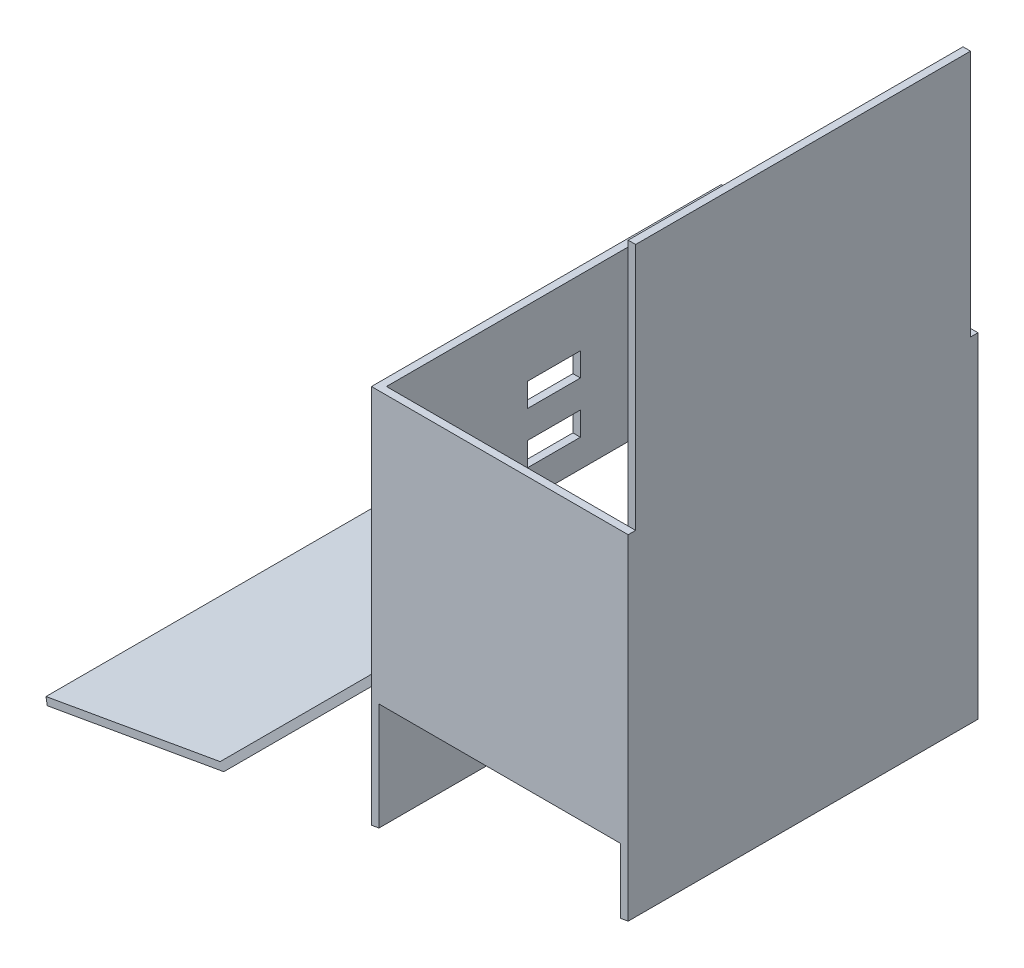
SolidWorks part; units mm, degrees
ref_plane "Front Plane" through (0, 0, 0) normal (0, 0, 1) x (1, 0, 0)
ref_plane "Top Plane" through (0, 0, 0) normal (0, 1, 0) x (1, 0, 0)
ref_plane "Right Plane" through (0, 0, 0) normal (1, 0, 0) x (0, 0, -1)
sketch "Sketch1" plane through (0, 0, 0) normal (0, 1, 0) x (1, 0, 0)
  line L1 (-102.5, 142) -> (102.5, 142)
  line L2 (-102.5, 142) -> (-102.5, -142)
  line L3 (-102.5, -142) -> (102.5, -142)
  line L4 (102.5, 142) -> (102.5, -142)
  line L5 (-102.5, 142) -> (102.5, -142) construction
  line L6 (-102.5, -142) -> (102.5, 142) construction
  line L7 (-108.85, 148.35) -> (108.85, 148.35)
  line L8 (-108.85, 148.35) -> (-108.85, -148.35)
  line L9 (-108.85, -148.35) -> (108.85, -148.35)
  line L10 (108.85, 148.35) -> (108.85, -148.35)
  line L11 (-108.85, 148.35) -> (108.85, -148.35) construction
  line L12 (-108.85, -148.35) -> (108.85, 148.35) construction
  point P0 (0, 0)
  point P5 (0, 0)
  dimension "D1" = 284
  dimension "D2" = 205
  dimension "D3" = 6.35
  dimension "D4" = 6.35
sketch3d "3DSketch1"
  line L0 (102.5, 150, 0) -> (102.5, 0, 0) construction
  line L1 (102.5, 0, 0) -> (0, 0, 0) construction
  line L2 (102.5, 0, 102.7399) -> (102.5, 0, -102.7399) construction
  line L3 (102.5, 0, 0) -> (102.5, -285, 0) construction
  line L4 (102.5, -285, -65.8407) -> (102.5, -285, 65.8407) construction
  line L5 (102.5, 0, -142) -> (102.5, 0, 142) construction
  point P2 (0, 0, 0)
  dimension "D1" = 150
  dimension "D2" = 285
ref_plane "Base Plane" through (51.25, -51.25, 0) normal (-0.7071, 0.7071, 0) x (0, 0, -1)
ref_plane "Launch Plane" through (51.8286, -293.9347, 0) normal (-0.1736, 0.9848, 0) x (0, 0, 1)
ref_plane "Box Bottom Plane (Approx)" through (0, -500, 0) normal (0, 1, 0) x (1, 0, 0)
extrude "Boss-Extrude1" add sketch "Sketch1" against normal up to surface (285 mm away) up to plane "Launch Plane"
sketch "Sketch7" plane through (0, 0, 0) normal (0, 0, 1) x (1, 0, 0)
  line L0 (102.5, 0) -> (-243.5111, -346.0111)
  line L2 (131.1629, 28.6629) -> (-28.6629, -131.1629) construction
  line L3 (55, 0) -> (-55, 0) construction
  line L4 (102.5, 0) -> (102.5, -8.9803)
  line L5 (102.5, -8.9803) -> (-240.4367, -351.917)
  line L6 (123.1531, -281.3583) -> (-19.4958, -306.5112) construction
  line L8 (-243.5111, -346.0111) -> (-391.2323, -372.0583)
  line L9 (-391.2323, -372.0583) -> (-390.1296, -378.3118)
  line L10 (-390.1296, -378.3118) -> (-240.4367, -351.917)
  point P4 (0, 0)
  dimension "D2" = 6.35
  dimension "D3" = 150
  dimension "D1" = 6.35
extrude "Boss-Extrude4" add sketch "Sketch7" against normal up to surface and the other way up to surface up to face at (0, -151.5368, -142) other way up to face at (0, -151.5368, 142)
sketch "Sketch8" plane through (0, 0, 0) normal (0, 1, 0) x (1, 0, 0)
  line L0 (108.85, 148.35) -> (108.85, -148.35) construction
  line L1 (102.5, 142) -> (108.85, 142)
  line L2 (102.5, 142) -> (102.5, -142)
  line L3 (102.5, -142) -> (108.85, -142)
  line L4 (108.85, 142) -> (108.85, -142)
  line L5 (-102.5, -142) -> (102.5, -142) construction
extrude "Boss-Extrude5" add sketch "Sketch8" along normal blind 210
sketch "Sketch4" plane through (0, 0, 0) normal (0, 0, 1) x (1, 0, 0)
  line L0 (-108.85, -211.35) -> (-102.5, -205)
  line L1 (-108.85, -143) -> (-102.5, -143)
  line L2 (-102.5, -205) -> (-102.5, 0) construction
  line L3 (-108.85, -211.35) -> (-108.85, -143)
  line L4 (-108.85, -322.2667) -> (-108.85, 0) construction
  line L5 (-102.5, -143) -> (-102.5, -205)
  line L7 (131.1629, 28.6629) -> (-28.6629, -131.1629) construction
  dimension "D2" = 62
extrude "Cut-Extrude1" cut sketch "Sketch4" against normal up to surface and the other way up to surface up to face at (-34.1667, -68.3333, -142) other way up to face at (-34.1667, -68.3333, 142)
sketch "Sketch6" plane through (0, 0, 0) normal (0, 0, 1) x (1, 0, 0)
  line L8 (-108.85, -99.5) -> (-102.5, -99.5)
  line L9 (-108.85, -99.5) -> (-108.85, -119.5)
  line L10 (-108.85, -119.5) -> (-102.5, -119.5)
  line L11 (-102.5, -99.5) -> (-102.5, -119.5)
  line L12 (-102.5, -143) -> (-102.5, -205) construction
  line L13 (-108.85, -56) -> (-102.5, -56)
  line L14 (-108.85, -56) -> (-108.85, -76)
  line L15 (-108.85, -76) -> (-102.5, -76)
  line L16 (-102.5, -56) -> (-102.5, -76)
  line L17 (-108.85, -143) -> (-102.5, -143) construction
  line L18 (-108.85, -211.35) -> (-108.85, -143) construction
  point P5 (-105.675, -99.5)
  dimension "D1" = 20
  dimension "D2" = 43.5
  dimension "D4" = 20
  dimension "D5" = 43.5
extrude "Cut-Extrude2" cut sketch "Sketch6" against normal mid plane 45
sketch "Sketch10" plane through (0, -500, 0) normal (0, 1, 0) x (1, 0, 0)
  line L0 (-102.5, 142) -> (-102.5, -142) construction
  line L1 (-102.5, 181.9729) -> (102.5, 181.9729)
  line L2 (-102.5, 181.9729) -> (-102.5, -202.4768)
  line L3 (-102.5, -202.4768) -> (102.5, -202.4768)
  line L4 (102.5, 181.9729) -> (102.5, -202.4768)
  line L5 (102.5, 142) -> (102.5, -142) construction
extrude "Cut-Extrude4" cut sketch "Sketch10" along normal blind 270
equation "\"Frisbee Width\"=274"
equation "\"D1@Sketch1\"=\"Frisbee Width\"+10"
equation "\"Wall Thickness\"= 6.35"
equation "\"D3@Sketch1\"=\"Wall Thickness\""
equation "\"D4@Sketch1\"=\"Wall Thickness\""
equation "\"D2@Sketch4\"=85-23"
equation "\"D2@Sketch7\"=\"Wall Thickness\""
equation "\"D1@Sketch7\"=\"Wall Thickness\""
